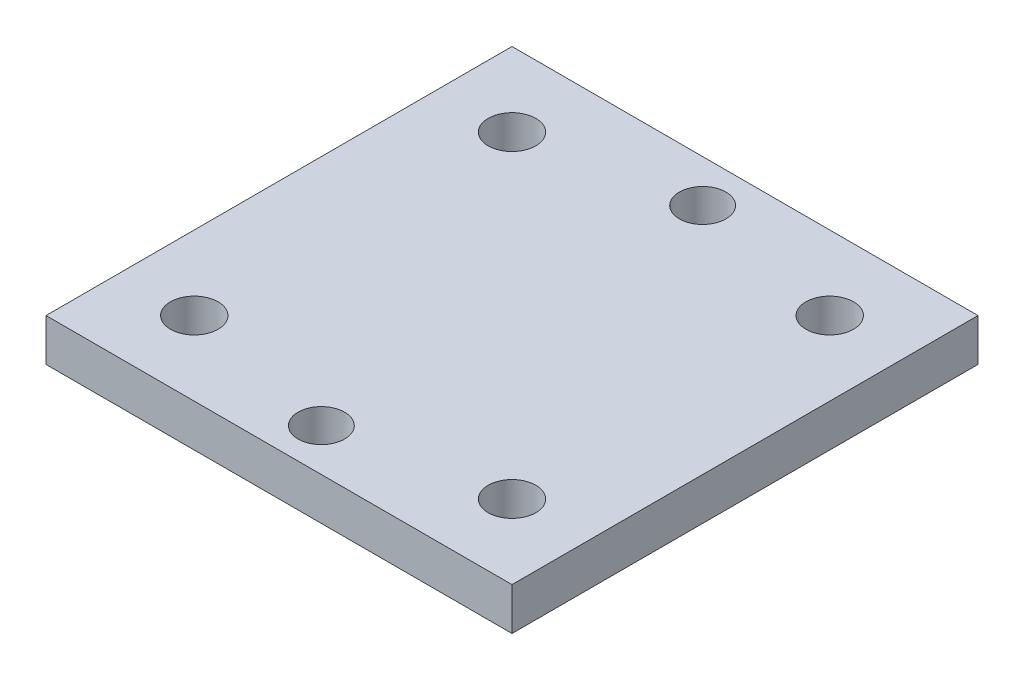
SolidWorks part; units mm, degrees
ref_plane "Front Plane" through (0, 0, 0) normal (0, 0, 1) x (1, 0, 0)
ref_plane "Top Plane" through (0, 0, 0) normal (0, 1, 0) x (1, 0, 0)
ref_plane "Right Plane" through (0, 0, 0) normal (1, 0, 0) x (0, 0, -1)
sketch "SK_Plate" plane through (0, 0, 0) normal (0, 1, 0) x (1, 0, 0)
  line L1 (-22, 22) -> (22, 22)
  line L2 (-22, 22) -> (-22, -22)
  line L3 (-22, -22) -> (22, -22)
  line L4 (22, 22) -> (22, -22)
  dimension "D1" = 44
  dimension "D2" = 44
  dimension "D3" = 22
  dimension "D4" = 22
extrude "EX_Plate" add sketch "SK_Plate" along normal blind 4
sketch "SK_Holes" plane through (0, 0, 0) normal (0, 1, 0) x (1, 0, 0)
  circle A0 centre (15, -15) radius 2.25
  circle A1 centre (-15, -15) radius 2.25
  circle A2 centre (15, 15) radius 2.25
  circle A3 centre (-15, 15) radius 2.25
  circle A4 centre (0, -18) radius 2.2
  circle A5 centre (0, 18) radius 2.2
  dimension "D3" = 4.5
  dimension "D6" = 4.5
  dimension "D9" = 4.5
  dimension "D12" = 4.5
  dimension "D14" = 4.4
  dimension "D16" = 4.4
  dimension "D1" = 15
  dimension "D2" = 15
  dimension "D4" = 15
  dimension "D5" = 15
  dimension "D7" = 15
  dimension "D8" = 15
  dimension "D10" = 15
  dimension "D11" = 15
  dimension "D13" = 18
  dimension "D15" = 18
extrude "CUT_Holes" cut sketch "SK_Holes" along normal blind 4
ref_axis "AX_X" through (0, 0, -24.2) along (0, 0, 1)
ref_axis "AX_Y" through (24.2, 0, 0) along (-1, 0, 0)
ref_axis "AX_Z" through (0, 4.2, 0) along (0, -1, 0)
